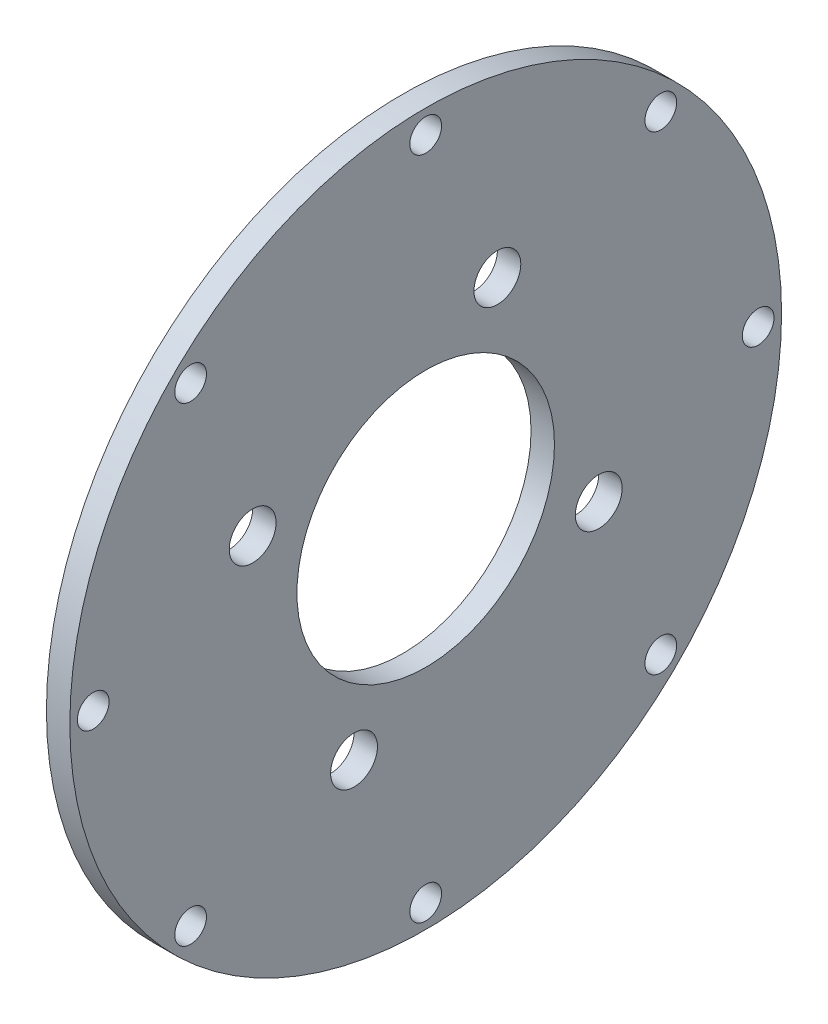
SolidWorks part; units mm, degrees
ref_plane "Front Plane" through (0, 0, 0) normal (0, 0, 1) x (1, 0, 0)
ref_plane "Top Plane" through (0, 0, 0) normal (0, 1, 0) x (1, 0, 0)
ref_plane "Right Plane" through (0, 0, 0) normal (1, 0, 0) x (0, 0, -1)
sketch "Sketch1" plane through (0, 0, 0) normal (1, 0, 0) x (0, 0, -1)
  line L0 (9.7202, 23.4665) -> (0, 0) construction
  circle A0 centre (0, 0) radius 48.26
  circle A1 centre (0, 45.085) radius 2.1527
  circle A2 centre (31.8799, 31.8799) radius 2.1527
  circle A3 centre (45.085, 0) radius 2.1527
  circle A4 centre (31.8799, -31.8799) radius 2.1527
  circle A5 centre (0, -45.085) radius 2.1527
  circle A6 centre (-31.8799, -31.8799) radius 2.1527
  circle A7 centre (-45.085, 0) radius 2.1527
  circle A8 centre (-31.8799, 31.8799) radius 2.1527
  circle A9 centre (0, 0) radius 17.4625
  circle A10 centre (9.7202, 23.4665) radius 3.175
  circle A11 centre (23.4665, -9.7202) radius 3.175
  circle A12 centre (-9.7202, -23.4665) radius 3.175
  circle A13 centre (-23.4665, 9.7202) radius 3.175
  dimension "D1" = 96.52
  dimension "D2" = 4.3053
  dimension "D4" = 34.925
  dimension "D5" = 6.35
  dimension "D3" = 45.085
  dimension "D6" = 25.4
extrude "Boss-Extrude1" add sketch "Sketch1" along normal blind 3.175
